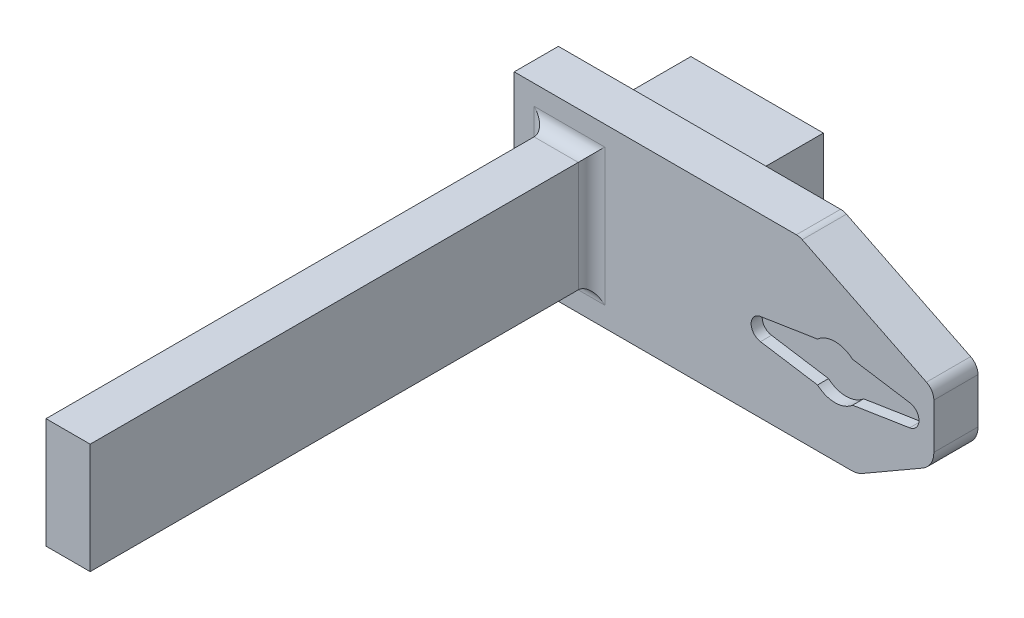
SolidWorks part; units mm, degrees
ref_plane "Front Plane" through (0, 0, 0) normal (0, 0, 1) x (1, 0, 0)
ref_plane "Top Plane" through (0, 0, 0) normal (0, 1, 0) x (1, 0, 0)
ref_plane "Right Plane" through (0, 0, 0) normal (1, 0, 0) x (0, 0, -1)
sketch "Sketch3" plane through (0, 0, 0) normal (0, 0, 1) x (1, 0, 0)
  line L1 (-22.6388, -7.4411) -> (22.3612, -7.4411)
  line L2 (-22.6388, -7.4411) -> (-22.6388, 7.5589)
  line L3 (-22.6388, 7.5589) -> (22.3612, 7.5589)
  line L4 (22.3612, -7.4411) -> (22.3612, 7.5589)
  dimension "D1" = 15
  dimension "D2" = 45
extrude "Boss-Extrude1" add sketch "Sketch3" against normal blind 10
sketch "Sketch2" plane through (0, 0, 0) normal (0, 0, 1) x (1, 0, 0)
  line L0 (-16.8881, 2.4697) -> (-3.9686, 4.5)
  line L1 (-16.8881, -2.4697) -> (-3.9686, -4.5)
  line L2 (3.9686, 4.5) -> (16.8881, 2.4697)
  line L3 (16.8881, -2.4697) -> (3.9686, -4.5)
  arc A0 (-16.8881, 2.4697) -> (-16.8881, -2.4697) centre (-16.5, 0) ccw
  arc A1 (-3.9686, 4.5) -> (3.9686, 4.5) centre (0, 0) cw
  arc A2 (-3.9686, -4.5) -> (3.9686, -4.5) centre (0, 0) ccw
  arc A3 (16.8881, -2.4697) -> (16.8881, 2.4697) centre (16.5, 0) ccw
extrude "Cut-Extrude1" cut sketch "Sketch2" against normal blind 2.5
sketch "Sketch11" plane through (0, -7.4411, 0) normal (0, -1, 0) x (1, 0, 0)
  line L0 (8.25, 0) -> (-8.25, 0) construction
  line L1 (22.3612, -10) -> (-22.6388, -10)
  line L2 (22.3612, -10) -> (22.3612, 0)
  line L3 (22.3612, 0) -> (-22.6388, 0)
  line L4 (-22.6388, -10) -> (-22.6388, 0)
  line L5 (-22.6388, -10) -> (-22.6388, 0) construction
extrude "Boss-Extrude5" add sketch "Sketch11" along normal blind 10
sketch "Sketch14" plane through (0, 7.5589, 0) normal (0, 1, 0) x (1, 0, 0)
  line L0 (-8.25, 0) -> (8.25, 0) construction
  line L1 (22.3612, 10) -> (-22.6388, 10)
  line L2 (22.3612, 10) -> (22.3612, 0)
  line L3 (22.3612, 0) -> (-22.6388, 0)
  line L4 (-22.6388, 10) -> (-22.6388, 0)
  line L5 (-22.6388, 10) -> (-22.6388, 0) construction
extrude "Boss-Extrude7" add sketch "Sketch14" along normal blind 15
sketch "Sketch20" plane through (-22.6388, 0, 0) normal (-1, 0, 0) x (0, 0, 1)
  line L0 (0, -22) -> (0, 22) construction
  line L1 (-10, 22.5589) -> (0, 22.5589)
  line L2 (-10, 22.5589) -> (-10, -17.4411)
  line L3 (-10, -17.4411) -> (0, -17.4411)
  line L4 (0, 22.5589) -> (0, -17.4411)
  line L5 (0, -17.4411) -> (-10, -17.4411) construction
extrude "Boss-Extrude10" add sketch "Sketch20" along normal blind 50
sketch "Sketch21" plane through (0, 0, 0) normal (0, 0, 1) x (1, 0, 0)
  line L1 (-65.1388, 15.0589) -> (-55.1388, 15.0589)
  line L2 (-65.1388, 15.0589) -> (-65.1388, -9.9411)
  line L3 (-65.1388, -9.9411) -> (-55.1388, -9.9411)
  line L4 (-55.1388, 15.0589) -> (-55.1388, -9.9411)
  line L5 (-72.6388, 22.5589) -> (22.3612, 22.5589) construction
  line L6 (-72.6388, -17.4411) -> (-72.6388, 22.5589) construction
  dimension "D1" = 7.5
  dimension "D2" = 25
  dimension "D3" = 7.5
  dimension "D4" = 10
extrude "Boss-Extrude11" add sketch "Sketch21" along normal blind 113.5
sketch "Sketch22" plane through (0, 0, -10) normal (0, 0, -1) x (-1, 0, 0)
  line L0 (72.6388, 22.5589) -> (72.6388, -17.4411) construction
  line L1 (42.6388, 5.5589) -> (72.6388, 5.5589)
  line L2 (42.6388, 5.5589) -> (42.6388, -0.4411)
  line L3 (42.6388, -0.4411) -> (72.6388, -0.4411)
  line L4 (72.6388, 5.5589) -> (72.6388, -0.4411)
  line L5 (42.6388, 5.5589) -> (72.6388, -0.4411) construction
  line L6 (42.6388, -0.4411) -> (72.6388, 5.5589) construction
  line L7 (72.6388, -17.4411) -> (-22.3612, -17.4411) construction
  point P0 (57.6388, 2.5589)
  dimension "D1" = 20
  dimension "D2" = 30
  dimension "D3" = 6
extrude "Boss-Extrude12" add sketch "Sketch22" along normal blind 30
sketch "Sketch23" plane through (0, -0.4411, 0) normal (0, -1, 0) x (1, 0, 0)
  line L1 (-72.6388, -10) -> (-42.6388, -10)
  line L2 (-72.6388, -10) -> (-72.6388, -40)
  line L3 (-72.6388, -40) -> (-42.6388, -40)
  line L4 (-42.6388, -10) -> (-42.6388, -40)
extrude "Boss-Extrude13" add sketch "Sketch23" along normal blind 8.5
fillet "Fillet1" radius 3 4 edges at (-60.1388, 15.0589, 0) (-65.1388, 2.5589, 0) (-55.1388, 2.5589, 0) (-60.1388, -9.9411, 0)
chamfer "Chamfer1" distance 15 angle 63.75 1 edges at (22.3612, 22.5589, -5) first distance on face at (22.3612, 2.5589, -5)
fillet "Fillet2" radius 3 2 edges at (-8.0558, 22.5589, -5) (22.3612, 7.5589, -5)
chamfer "Chamfer2" distance 10 angle 60 1 edges at (22.3612, -17.4411, -5) first distance on face at (22.3612, -5.8739, -5)
fillet "Fillet3" radius 5 2 edges at (5.0406, -17.4411, -5) (22.3612, -7.4411, -5)
